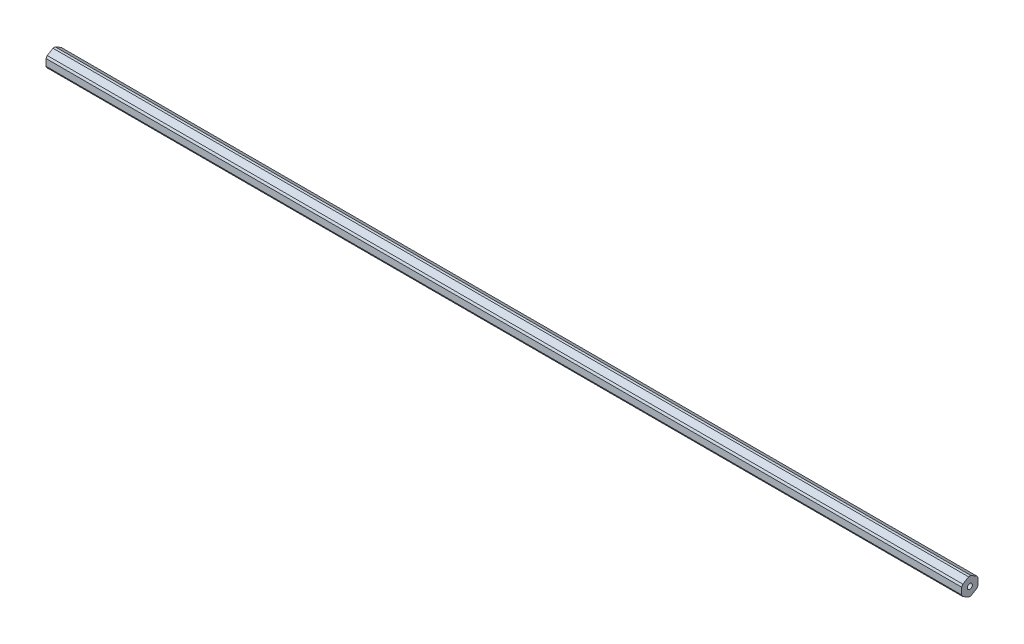
SolidWorks part; units mm, degrees
material "6061 Alloy"
ref_plane "Front Plane" through (0, 0, 0) normal (0, 0, 1) x (1, 0, 0)
ref_plane "Top Plane" through (0, 0, 0) normal (0, 1, 0) x (1, 0, 0)
ref_plane "Right Plane" through (0, 0, 0) normal (1, 0, 0) x (0, 0, -1)
ref_plane "Plane1" through (914.4, 0, 0) normal (1, 0, 0) x (0, 0, -1)
sketch "Sketch1" plane through (914.4, 0, 0) normal (1, 0, 0) x (0, 0, -1)
  line L0 (-5.4343, -4.1949) -> (-0.9157, -6.8037)
  line L1 (0.9157, -6.8037) -> (5.4343, -4.1949)
  line L2 (6.35, -2.6088) -> (6.35, 2.6088)
  line L3 (5.4343, 4.1949) -> (0.9157, 6.8037)
  line L4 (-0.9157, 6.8037) -> (-5.4343, 4.1949)
  line L5 (-6.35, 2.6088) -> (-6.35, -2.6088)
  circle A0 centre (0, 0) radius 1.9939
  arc A1 (-6.35, -2.6088) -> (-5.4343, -4.1949) centre (0, 0) ccw
  arc A2 (-0.9157, -6.8037) -> (0.9157, -6.8037) centre (0, 0) ccw
  arc A3 (5.4343, -4.1949) -> (6.35, -2.6088) centre (0, 0) ccw
  arc A4 (6.35, 2.6088) -> (5.4343, 4.1949) centre (0, 0) ccw
  arc A5 (0.9157, 6.8037) -> (-0.9157, 6.8037) centre (0, 0) ccw
  arc A6 (-5.4343, 4.1949) -> (-6.35, 2.6088) centre (0, 0) ccw
extrude "Boss-Extrude1" add sketch "Sketch1" against normal mid plane 711.2
equation "\"Hex Length\"= 28in"
equation "\"D1@Boss-Extrude1\"=\"Hex Length\""
